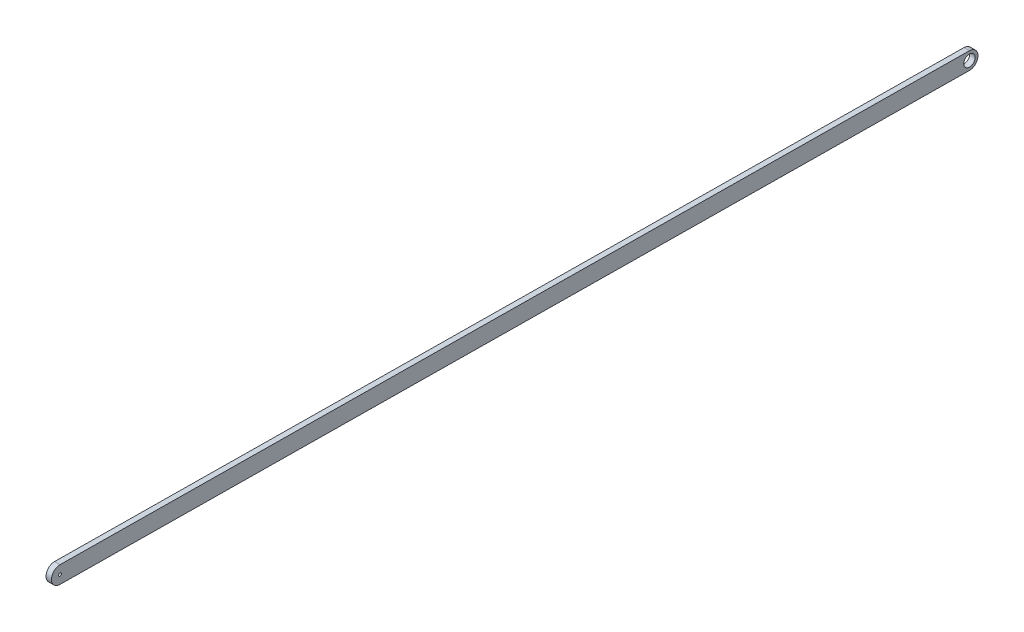
SolidWorks part; units mm, degrees
ref_plane "Front Plane" through (0, 0, 0) normal (0, 0, 1) x (1, 0, 0)
ref_plane "Top Plane" through (0, 0, 0) normal (0, 1, 0) x (1, 0, 0)
ref_plane "Right Plane" through (0, 0, 0) normal (1, 0, 0) x (0, 0, -1)
sketch "Sketch1" plane through (0, 0, 0) normal (1, 0, 0) x (0, 0, -1)
  line L0 (332.7718, -0.5868) -> (-173.3047, 4.7622)
  line L5 (-173.4053, -4.7622) -> (332.6712, -10.1113)
  circle A0 centre (-173.355, 0) radius 0.7938
  circle A1 centre (332.7215, -5.349) radius 3.175
  circle A8 centre (-173.355, 0) radius 0.7937 construction
  circle A9 centre (-173.355, 0) radius 4.7625
  circle A10 centre (332.7215, -5.349) radius 4.7625
  dimension "D4" = 9.525
  dimension "D1" = 6.35
  dimension "D2" = 1.5875
  dimension "D3" = 9.525
extrude "Boss-Extrude1" add sketch "Sketch1" along normal blind 3.0378 contours A9 A0 | A10 L0 A9 L5 | A10 A1 region at (0, -2.6745, -79.6833) region at (0, -2.094, -336.0111) region at (0, 3.255, 170.0654)
